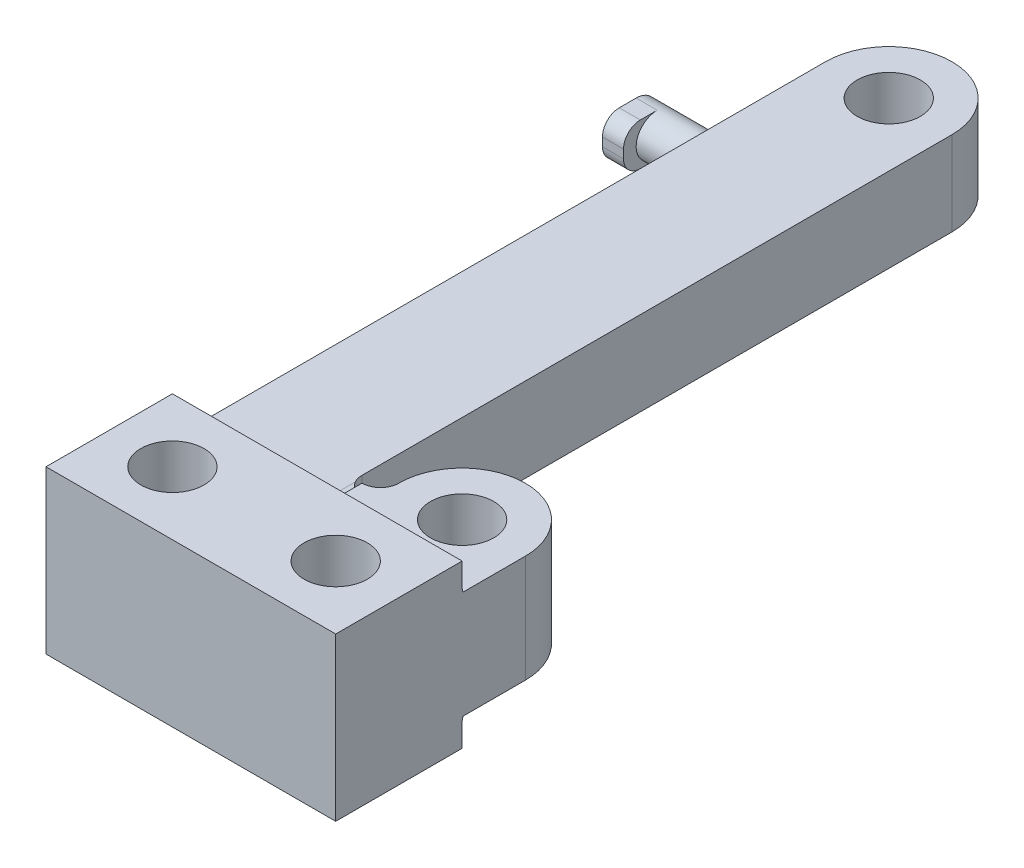
SolidWorks part; units mm, degrees
material "3.0205 (EN-AW 1200)"
ref_plane "Front Plane" through (0, 0, 0) normal (0, 0, 1) x (1, 0, 0)
ref_plane "Top Plane" through (0, 0, 0) normal (0, 1, 0) x (1, 0, 0)
ref_plane "Right Plane" through (0, 0, 0) normal (1, 0, 0) x (0, 0, -1)
sketch "Sketch2" plane through (0, 0, 0) normal (0, 1, 0) x (1, 0, 0)
  line L0 (-6.875, 0) -> (6.875, 0)
  line L1 (-6.875, -6) -> (6.875, -6)
  line L2 (-6.875, -6) -> (-6.875, 6)
  line L5 (-6.875, -6) -> (6.875, 6) construction
  line L6 (-6.875, 6) -> (6.875, -6) construction
  line L7 (-0.875, 6) -> (-0.875, 31)
  line L9 (-6.875, 31) -> (-6.875, 6)
  line L10 (0, -8.1975) -> (0, 6) construction
  line L11 (6.875, 6) -> (-0.875, 6) construction
  line L12 (-3.875, -3) -> (-3.875, 34) construction
  line L13 (-0.875, 3) -> (-0.875, 6)
  line L14 (6.875, 3) -> (-0.875, 3) construction
  line L15 (6.875, 3) -> (6.875, -6)
  line L16 (6.875, 3) -> (6.875, 6) construction
  line L17 (0, 0) -> (0, 2.125)
  circle A4 centre (3.875, -3) radius 1.5
  circle A5 centre (3.875, 3) radius 1.5
  circle A6 centre (-3.875, -3) radius 1.5
  circle A7 centre (-3.875, 31) radius 1.5
  arc A8 (-6.875, 31) -> (-0.875, 31) centre (-3.875, 31) cw
  arc A9 (6.875, 3) -> (0.875, 3) centre (3.875, 3) ccw
  arc A10 (0.875, 3) -> (-0.875, 3) centre (0, 3) cw
  point P0 (0, 0)
  dimension "D3" = 3
  dimension "D4" = 3
  dimension "D8" = 3
  dimension "D1" = 13.75
  dimension "D2" = 12
  dimension "D5" = 3
  dimension "D6" = 3
  dimension "D7" = 7.75
  dimension "D9" = 34
extrude "Boss-Extrude1" add sketch "Sketch2" along normal mid plane 7.7 contours L15 L0 L2 L1 A6 A4 region at (0, 0, 3)
extrude "Boss-Extrude2" add sketch "Sketch2<4>" along normal mid plane 4 contours L17 A10 L13 L7 A8 L9 L2 L0 A7 region at (-3.8395, 0, -16.0052)
sketch "Sketch2<4>" plane through (0, 0, 0) normal (0, 1, 0) x (1, 0, 0) same geometry as "Sketch2"
extrude "Boss-Extrude3" add sketch "Sketch2<6>" along normal mid plane 5.1 contours A9 A10 L17 L0 L15 A5 region at (0.0912, 0, -1.0625)
sketch "Sketch2<6>" plane through (0, 0, 0) normal (0, 1, 0) x (1, 0, 0) same geometry as "Sketch2"
fillet "Fillet1" radius 0.8 2 edges at (-3.4375, -2, 0) (-3.4375, 2, 0)
fillet "Fillet2" radius 0.8 2 edges at (0, 2, -1.4625) (0, -2, -1.4625)
sketch "Sketch3" plane through (-6.875, 0, 0) normal (-1, 0, 0) x (0, 0, 1)
  line L0 (0, 0) -> (-34, 0) construction
  line L1 (-34, 2) -> (-34, -2) construction
  line L2 (-26.01, -1) -> (-25.21, -1)
  line L3 (-24.41, -0.2) -> (-24.41, 0.2)
  line L4 (-25.21, 1) -> (-26.01, 1)
  circle A0 centre (-26.01, 0) radius 1
  arc A1 (-24.41, 0.2) -> (-25.21, 1) centre (-25.21, 0.2) ccw
  arc A2 (-24.41, -0.2) -> (-25.21, -1) centre (-25.21, -0.2) cw
  dimension "D1" = 0.8
  dimension "D2" = 2
  dimension "D3" = 0.8
  dimension "D4" = 26.01
extrude "Boss-Extrude4" add sketch "Sketch3" along normal blind 3 contours A0 L0 | L0 A0 region at (-6.875, -0.4244, -26.01) region at (-6.875, 0.4244, -26.01)
extrude "Boss-Extrude5" add sketch "Sketch3<3>" along direction (-1, 0, 0) on the side of the normal blind 1 from offset 3 contours L3 L0 A0 L2 A2 | L0 L3 A1 L4 A0 | A0 L0 | L0 A0 region at (-6.875, -0.5225, -24.9004) region at (-6.875, 0.5225, -24.9004) region at (-6.875, -0.4244, -26.01) region at (-6.875, 0.4244, -26.01)
sketch "Sketch3<3>" plane through (-6.875, 0, 0) normal (-1, 0, 0) x (0, 0, 1) same geometry as "Sketch3"
